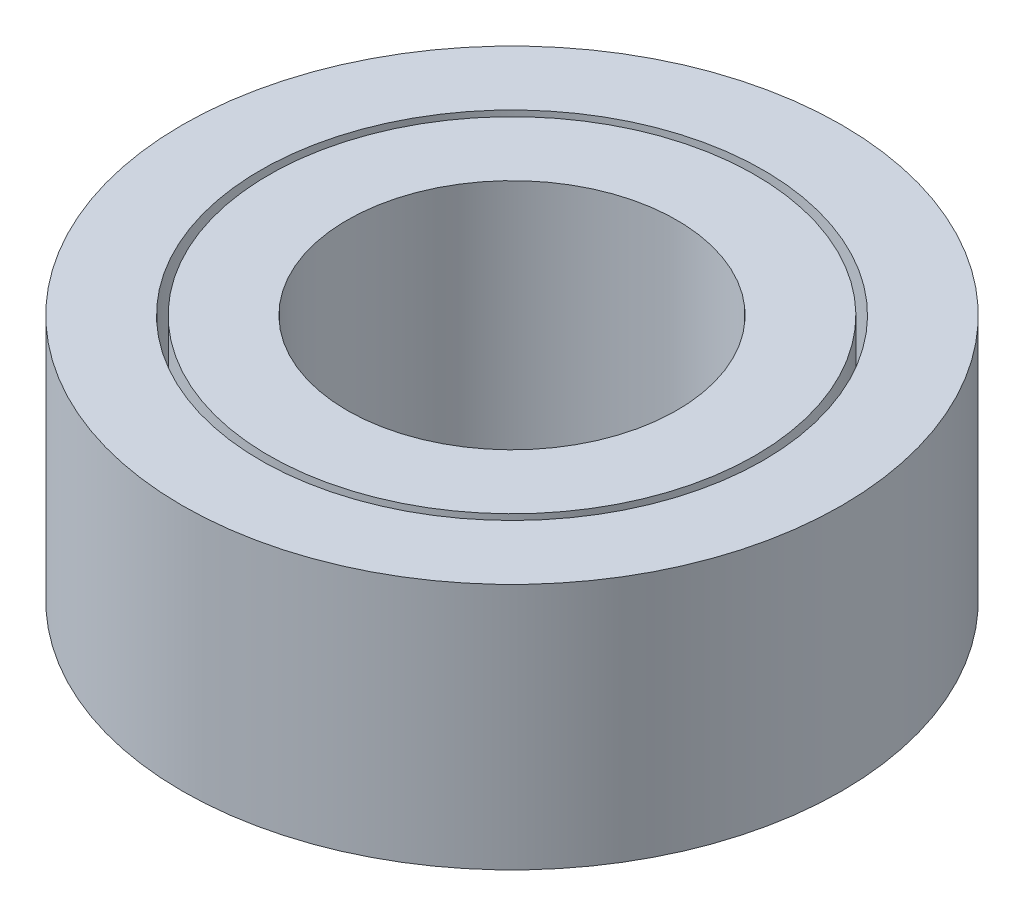
SolidWorks part; units mm, degrees
ref_plane "前视基准面" through (0, 0, 0) normal (0, 0, 1) x (1, 0, 0)
ref_plane "上视基准面" through (0, 0, 0) normal (0, 1, 0) x (1, 0, 0)
ref_plane "右视基准面" through (0, 0, 0) normal (1, 0, 0) x (0, 0, -1)
other "Configuration Table"
sketch "草图1" plane through (0, 0, 0) normal (0, 1, 0) x (1, 0, 0)
  circle A0 centre (0, 0) radius 2
  circle A1 centre (0, 0) radius 4
  circle A2 centre (0, 0) radius 3
  dimension "D1" = 8
  dimension "D2" = 4
  dimension "D3" = 6
extrude "凸台-拉伸1" add sketch "草图1" along normal blind 3 contours A1 A2 region at (-3.8869, 0, 0)
extrude "凸台-拉伸2" add sketch "草图1<3>" along normal blind 3 contours A2 A0 region at (-2.9151, 0, 0)
sketch "草图1<3>" plane through (0, 0, 0) normal (0, 1, 0) x (1, 0, 0) same geometry as "草图1"
extrude "切除-拉伸-薄壁2" cut sketch "草图1<5>" along normal blind 3 thin contours A2 thin type mid plane wall 0.1
sketch "草图1<5>" plane through (0, 0, 0) normal (0, 1, 0) x (1, 0, 0) same geometry as "草图1"
